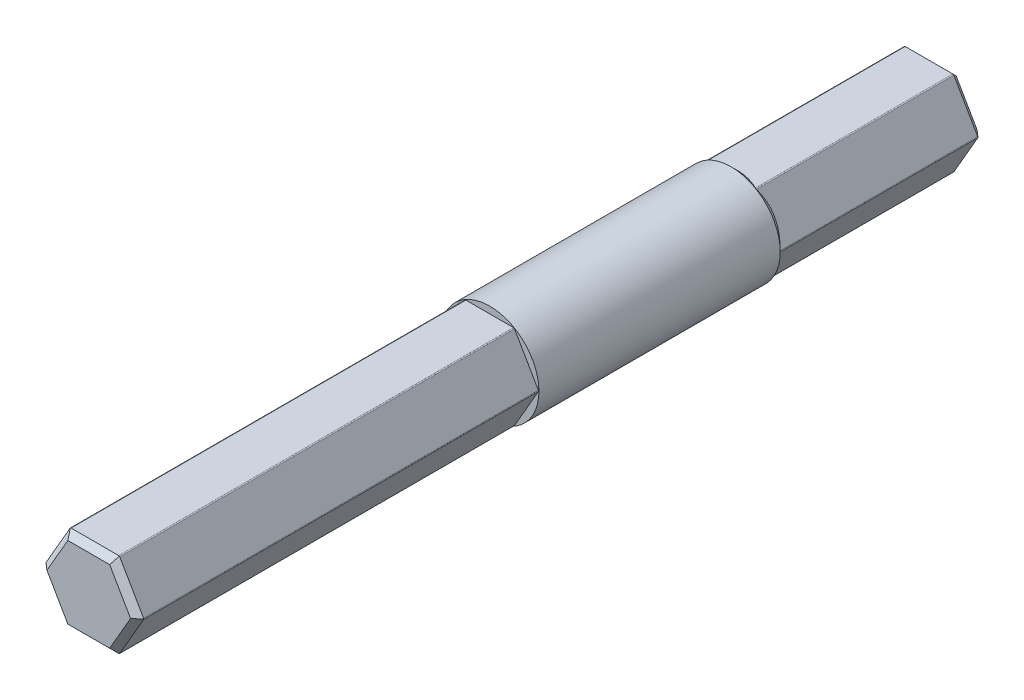
SolidWorks part; units mm, degrees
material "PETG"
ref_plane "Front Plane" through (0, 0, 0) normal (0, 0, 1) x (1, 0, 0)
ref_plane "Top Plane" through (0, 0, 0) normal (0, 1, 0) x (1, 0, 0)
ref_plane "Right Plane" through (0, 0, 0) normal (1, 0, 0) x (0, 0, -1)
sketch "Sketch1" plane through (0, 0, 0) normal (0, 0, 1) x (1, 0, 0)
  circle A0 centre (0, 0) radius 3.975
  dimension "Shaft Dia" = 7.95
extrude "Boss-Extrude1" add sketch "Sketch1" along normal blind 20
sketch "Sketch2" plane through (0, 0, 20) normal (0, 0, 1) x (1, 0, 0)
  line L1 (4, 0) -> (2, 3.4641) construction
  line L2 (2, 3.4641) -> (-2, 3.4641) construction
  line L3 (-2, 3.4641) -> (-4, 0) construction
  line L4 (-4, 0) -> (-2, -3.4641) construction
  line L5 (-2, -3.4641) -> (2, -3.4641) construction
  line L6 (2, -3.4641) -> (4, 0) construction
  line L7 (3.9567, 0) -> (1.9783, 3.4266)
  line L8 (1.9783, 3.4266) -> (-1.9783, 3.4266)
  line L9 (-1.9783, 3.4266) -> (-3.9567, 0)
  line L10 (-3.9567, 0) -> (-1.9783, -3.4266)
  line L11 (-1.9783, -3.4266) -> (1.9783, -3.4266)
  line L12 (1.9783, -3.4266) -> (3.9567, 0)
  circle A0 centre (0, 0) radius 3.4641 construction
  circle A1 centre (0, 0) radius 3.4266 construction
  dimension "Hex Circumscribed Nominal Dia" = 8
  dimension "Hex Flat To Flat Offset" = 0.0375
extrude "Boss-Extrude2" add sketch "Sketch2" along normal blind 32.4
sketch "Sketch3" plane through (0, 0, 0) normal (0, 0, -1) x (-1, 0, 0)
  line L0 (-1.9783, 3.4266) -> (1.9783, 3.4266) construction
  line L13 (3.9567, 0) -> (1.9783, 3.4266)
  line L14 (1.9783, 3.4266) -> (-1.9783, 3.4266)
  line L15 (-1.9783, 3.4266) -> (-3.9567, 0)
  line L16 (-3.9567, 0) -> (-1.9783, -3.4266)
  line L17 (-1.9783, -3.4266) -> (1.9783, -3.4266)
  line L18 (1.9783, -3.4266) -> (3.9567, 0)
  circle A1 centre (0, 0) radius 3.4266 construction
extrude "Boss-Extrude3" add sketch "Sketch3" along normal blind 16
chamfer "Chamfer1" distance 0.5 angle 45 12 edges at (0, -3.4266, 52.4) (-2.9675, -1.7133, 52.4) (-2.9675, 1.7133, 52.4) (0, 3.4266, 52.4) (2.9675, 1.7133, 52.4) (2.9675, -1.7133, 52.4) (0, -3.4266, -16) (2.9675, -1.7133, -16) (2.9675, 1.7133, -16) (0, 3.4266, -16) (-2.9675, 1.7133, -16) (-2.9675, -1.7133, -16)
fillet "Fillet1" radius 0.1 12 edges at (-1.9783, 3.4266, -7.75) (-3.9567, 0, -7.75) (1.9783, 3.4266, -7.75) (3.9567, 0, -7.75) (1.9783, -3.4266, -7.75) (-1.9783, -3.4266, -7.75) (1.9783, -3.4266, 35.95) (-1.9783, -3.4266, 35.95) (-3.9567, 0, 35.95) (-1.9783, 3.4266, 35.95) (3.9567, 0, 35.95) (1.9783, 3.4266, 35.95)
chamfer "Chamfer2" distance 0.5 angle 45 1 edges at (3.975, 0, 0)
equation "\"tol_dia_id_intfc\" = 0.0500mm ' For hole diameters - Interference fit"
equation "\"tol_dia_id_slip\"  = 0.0750mm ' For hole diameters - Slip fit"
equation "\"tol_dia_id_clear\" = 0.1000mm ' For hole diameters - Clearance fit"
equation "\"tol_dia_od_intfc\" = 0.0500mm ' For shaft diameters - Interference fit"
equation "\"tol_dia_od_slip\"  = 0.0750mm ' For shaft diameters - Slip fit"
equation "\"tol_dia_od_clear\" = 0.1000mm ' For shaft diameters - Clearance fit"
equation "\"tol_general_intfc\"= 0.0250mm ' For general parts (Horiz) - Interference fit"
equation "\"tol_general_slip\" = 0.0375mm ' For general parts (Horiz) - Slip fit"
equation "\"tol_general_clear\"= 0.0500mm ' For general parts (Horiz) - Clearance fit"
equation "\"tol_layer_intfc\"  = 0.0250mm ' For all parts (Vert) - Interference fit"
equation "\"tol_layer_slip\"   = 0.0375mm ' For all parts (Vert) - Slip fit"
equation "\"tol_layer_clear\"  = 0.0500mm ' For all parts (Vert) - Clearance fit"
equation "\"tol_corner_rad\"   = 0.100mm ' For corners that fit into other parts"
equation "\"Shaft Dia@Sketch1\" = \"nominal_dia\" - \"tol_dia_od_intfc\""
equation "\"nominal_dia\"= 8.00mm"
equation "\"Hex Circumscribed Nominal Dia@Sketch2\" = \"nominal_dia\""
equation "\"Hex Flat To Flat Offset@Sketch2\"=\"tol_general_slip\""
equation "\"D1@Fillet1\"=\"tol_corner_rad\""
equation "\"D1@Boss-Extrude2\"=32.50mm-\"tol_layer_clear\"*2"
